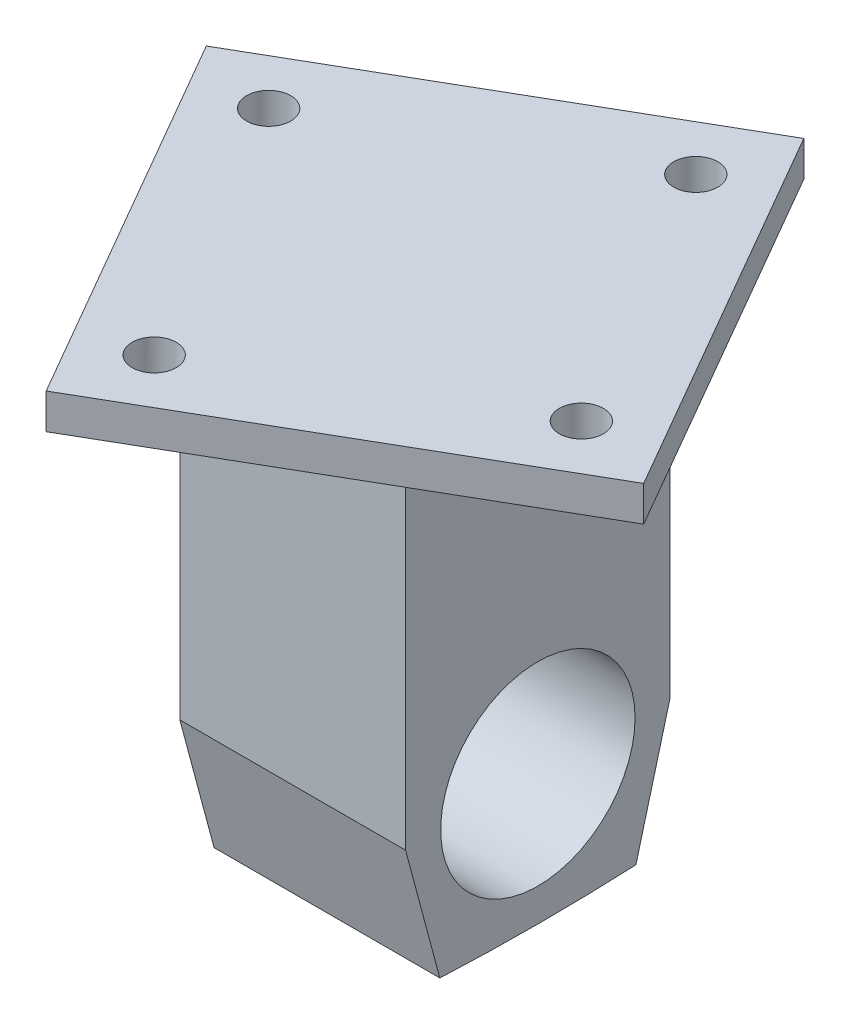
SolidWorks part; units mm, degrees
material "ABS"
ref_plane "Front Plane" through (0, 0, 0) normal (0, 0, 1) x (1, 0, 0)
ref_plane "Top Plane" through (0, 0, 0) normal (0, 1, 0) x (1, 0, 0)
ref_plane "Right Plane" through (0, 0, 0) normal (1, 0, 0) x (0, 0, -1)
sketch "Sketch1" plane through (0, 0, 0) normal (0, 1, 0) x (1, 0, 0)
  line L1 (-16.256, -19.05) -> (16.256, -19.05)
  line L2 (-16.256, -19.05) -> (-16.256, 19.05)
  line L3 (-16.256, 19.05) -> (16.256, 19.05)
  line L4 (16.256, -19.05) -> (16.256, 19.05)
  line L5 (-16.256, -19.05) -> (16.256, 19.05) construction
  line L6 (-16.256, 19.05) -> (16.256, -19.05) construction
  point P0 (0, 0)
extrude "Boss-Extrude1" add sketch "Sketch1" along normal blind 50.292
sketch "Sketch2" plane through (16.256, 0, 0) normal (1, 0, 0) x (0, 0, -1)
  line L0 (-19.05, 0) -> (-14.1195, -18.4009)
  line L1 (19.05, 0) -> (14.1195, -18.4009)
  line L2 (-19.05, 0) -> (19.05, 0)
  line L3 (-19.05, 0) -> (19.05, 0) construction
  arc A1 (14.1195, -18.4009) -> (-14.1195, -18.4009) centre (0, 281.2546) cw
  dimension "D1" = 19.05
  dimension "D2" = 19.05
  dimension "D3" = 75
  dimension "D4" = 75
extrude "Boss-Extrude2" add sketch "Sketch2" against normal up to vertex (32.512 mm away) contours L0 A1 L1 L2 up to point (-16.256, 0, -19.05)
sketch "Sketch3" plane through (16.256, 0, 0) normal (1, 0, 0) x (0, 0, -1)
  circle A0 centre (0, 0) radius 14
extrude "Cut-Extrude1" cut sketch "Sketch3" against normal blind 127 contours A0
sketch "Sketch4" plane through (0, 50.292, 0) normal (0, 1, 0) x (1, 0, 0)
  line L0 (-46.8473, 12.5527) -> (46.8473, -12.5527) construction
  line L5 (-13.6389, -50.901) -> (13.6389, 50.901) construction
  line L6 (43.0243, -11.5283) -> (-11.5283, -43.0243)
  line L11 (-11.5283, -43.0243) -> (-43.0243, 11.5283)
  line L12 (-43.0243, 11.5283) -> (11.5283, 43.0243)
  line L13 (11.5283, 43.0243) -> (43.0243, -11.5283)
  line L14 (-11.5283, -43.0243) -> (11.5283, 43.0243) construction
  line L15 (-43.0243, 11.5283) -> (43.0243, -11.5283) construction
  point P1 (0, 0)
  point P4 (0, 0)
  point P11 (0, 0)
  dimension "D1" = 62.992
  dimension "D2" = 62.992
  dimension "D3" = 0
  dimension "D4" = 0
extrude "Boss-Extrude3" add sketch "Sketch4" along normal blind 5.08
sketch "Sketch5" plane through (0, 55.372, 0) normal (0, 1, 0) x (1, 0, 0)
  line L2 (30.7571, -8.2413) -> (43.0243, -11.5283) construction
  line L3 (-8.2413, -30.7571) -> (-11.5283, -43.0243) construction
  line L4 (-30.7571, 8.2413) -> (-43.0243, 11.5283) construction
  line L5 (8.2413, 30.7571) -> (11.5283, 43.0243) construction
  line L6 (11.5283, 43.0243) -> (-43.0243, 11.5283) construction
  line L7 (43.0243, -11.5283) -> (11.5283, 43.0243) construction
  line L8 (-43.0243, 11.5283) -> (-11.5283, -43.0243) construction
  circle A0 centre (30.7571, -8.2413) radius 3.175
  circle A1 centre (-8.2413, -30.7571) radius 3.175
  circle A2 centre (8.2413, 30.7571) radius 3.175
  circle A3 centre (-30.7571, 8.2413) radius 3.175
  dimension "D2" = 6.35
  dimension "D4" = 6.35
  dimension "D11" = 6.35
  dimension "D12" = 6.35
  dimension "D1" = 12.7
  dimension "D3" = 45
  dimension "D5" = 12.7
  dimension "D6" = 45
  dimension "D7" = 12.7
  dimension "D8" = 45
  dimension "D9" = 12.7
  dimension "D10" = 45
extrude "Cut-Extrude2" cut sketch "Sketch5" against normal through all
